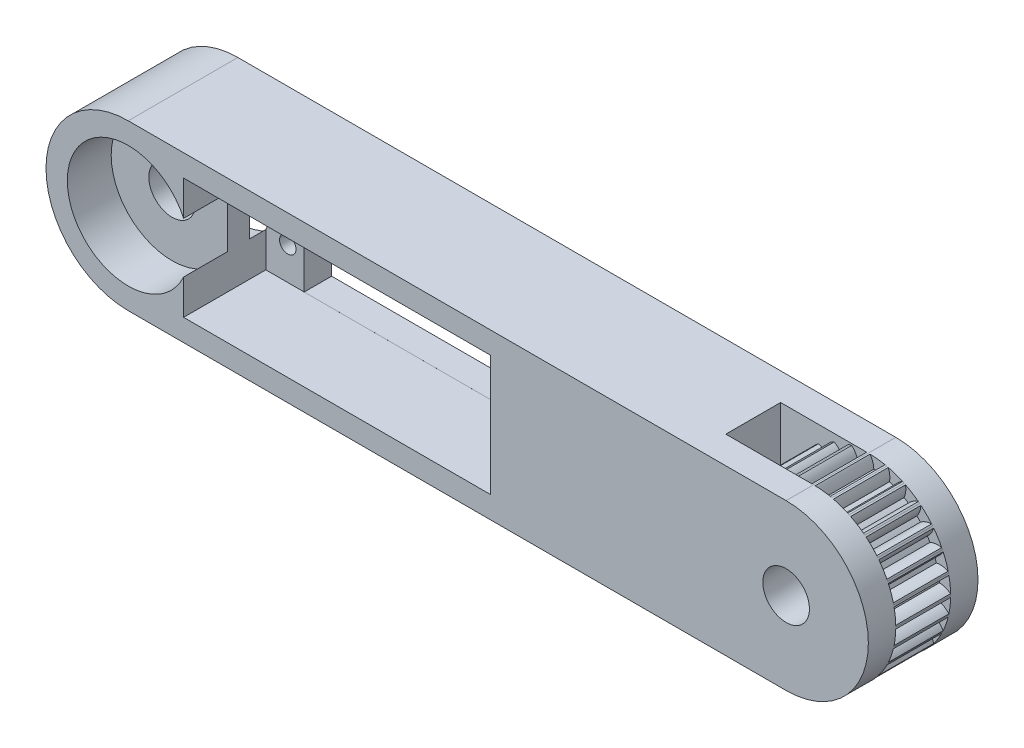
SolidWorks part; units mm, degrees
ref_plane "Front Plane" through (0, 0, 0) normal (0, 0, 1) x (1, 0, 0)
ref_plane "Top Plane" through (0, 0, 0) normal (0, 1, 0) x (1, 0, 0)
ref_plane "Right Plane" through (0, 0, 0) normal (1, 0, 0) x (0, 0, -1)
sketch "Sketch1" plane through (0, 0, 0) normal (0, 0, 1) x (1, 0, 0)
  line L0 (0, 0) -> (120, 0) construction
  line L1 (0, 15) -> (120, 15)
  line L2 (0, -15) -> (120, -15)
  circle A0 centre (0, 0) radius 15
  circle A1 centre (120, 0) radius 15
  dimension "D1" = 30
  dimension "D2" = 120
extrude "Boss-Extrude1" add sketch "Sketch1" along normal mid plane 20 contours A0 | A0 L0 A1 L1 | L0 A0 L2 A1 | A1 region at (60, 7.777, 0) region at (10.3066, -10.3066, 0) region at (60, -7.777, 0) region at (109.6934, 10.3066, 0)
sketch "Sketch9" plane through (0, 0, 10) normal (0, 0, 1) x (1, 0, 0)
  line L0 (0, 0) -> (120, 0) construction
  line L1 (104, 21.8549) -> (104, -22.7594)
  line L2 (104, -22.7594) -> (146.071, -22.7594)
  line L3 (146.071, -22.7594) -> (146.071, 21.8549)
  line L4 (146.071, 21.8549) -> (104, 21.8549)
  dimension "D1" = 120
  dimension "D2" = 16
sketch "Sketch3" plane through (0, 0, 10) normal (0, 0, 1) x (1, 0, 0)
  line L0 (0, 0) -> (120, 0) construction
  line L1 (120, 0) -> (120, -10.6139) construction
  line L2 (120.3, 15) -> (119.7, 15)
  circle A4 centre (120, 0) radius 13
  circle A5 centre (120, 0) radius 4.25
  circle A6 centre (120, 0) radius 15 construction
  arc A7 (119.7, 15) -> (119, 12.9615) centre (122.738, 12.8174) ccw
  arc A8 (120.3, 15) -> (121, 12.9615) centre (117.262, 12.8174) cw
  point P12 (119.2, 14.0322)
  point P14 (120, 15)
  arc M6 (120, -15) -> (120, 15) centre (120, 0) ccw
  line M7 (120, 15) -> (0, 15)
  dimension "D2" = 26
  dimension "D3" = 8.5
  dimension "D5" = 0.8
  dimension "D7" = 30
  dimension "D1" = 120
  dimension "D4" = 1
  dimension "D6" = 0.6
extrude "Cut-Extrude5" cut sketch "Sketch3" against normal through all contours A5 region at (120, 0, 10)
sketch "Sketch4" plane through (0, 0, 10) normal (0, 0, 1) x (1, 0, 0)
  line L0 (0, 0) -> (120, 0) construction
  line L2 (59.1, -11) -> (17.1, -11)
  line L3 (59.1, -11) -> (59.1, 11)
  line L4 (59.1, 11) -> (17.1, 11)
  line L5 (17.1, -11) -> (17.1, 11)
  line L6 (59.1, -11) -> (17.1, 11) construction
  line L7 (59.1, 11) -> (17.1, -11) construction
  circle A0 centre (0, 0) radius 4.25
  circle A1 centre (0, 0) radius 11.11
  point P4 (38.1, 0)
  dimension "D3" = 8.5
  dimension "D4" = 22.22
  dimension "D1" = 22
  dimension "D2" = 42
  dimension "D5" = 17.1
extrude "Cut-Extrude8" cut sketch "Sketch4" against normal through all contours A0 | L3 L2 L5 L4
sketch "Sketch5" plane through (0, 0, -10) normal (0, 0, -1) x (-1, 0, 0)
  circle A0 centre (0, 0) radius 11.11
  dimension "D1" = 22.22
extrude "Cut-Extrude10" cut sketch "Sketch5" against normal blind 8
mirror "Mirror2" about plane through (0, 0, 0) normal (0, 0, 1) of "Cut-Extrude10"
sketch "Sketch7" plane through (0, 0, 10) normal (0, 0, 1) x (1, 0, 0)
  line L0 (38.1, 11) -> (38.1, -11) construction
  line L1 (59.1, 11) -> (17.1, 11) construction
  line L2 (59.1, -11) -> (17.1, -11) construction
  line L4 (66.1, -11.0014) -> (10.1, -11.0014)
  line L5 (66.1, -11.0014) -> (66.1, 11.0014)
  line L6 (66.1, 11.0014) -> (10.1, 11.0014)
  line L7 (10.1, -11.0014) -> (10.1, 11.0014)
  line L8 (66.1, -11.0014) -> (10.1, 11.0014) construction
  line L9 (66.1, 11.0014) -> (10.1, -11.0014) construction
  point P6 (38.1, 0)
  dimension "D1" = 56
extrude "Cut-Extrude12" cut sketch "Sketch7" against normal blind 15
sketch "Sketch8" plane through (0, 0, -5) normal (0, 0, 1) x (1, 0, 0)
  line L0 (38.1, 11.0014) -> (38.1, -11.0014) construction
  line L1 (66.1, 11.0014) -> (10.1, 11.0014) construction
  line L2 (10.1, -11.0014) -> (66.1, -11.0014) construction
  line L3 (14.1, 5) -> (14.1, -5) construction
  line L4 (62.1, 5) -> (62.1, -5) construction
  line L5 (38.1, 0) -> (25.4065, 0) construction
  line L6 (14.1, 0) -> (20.8073, 0) construction
  circle A0 centre (14.1, 5) radius 1.5
  circle A1 centre (14.1, -5) radius 1.5
  circle A2 centre (62.1, -5) radius 1.5
  circle A3 centre (62.1, 5) radius 1.5
  dimension "D1" = 3
  dimension "D2" = 10
  dimension "D3" = 48
extrude "Cut-Extrude13" cut sketch "Sketch8" against normal blind 14 contours A0 | A1 | A2 | A3 region at (14.1, 5, -5) region at (14.1, -5, -5) region at (62.1, -5, -5)
sketch "Sketch13" plane through (0, 0, 0) normal (0, 0, 1) x (1, 0, 0)
  line L0 (120, 15) -> (104, 15)
  line L3 (104, 15) -> (104, -15)
  line L5 (104, -15) -> (120, -15)
  arc A0 (120, -15) -> (120, 15) centre (120, 0) ccw
  dimension "D1" = 16
extrude "Cut-Extrude17" cut sketch "Sketch13" against normal mid plane 10
extrude "Boss-Extrude2" add sketch "Sketch3<6>" against normal blind 10 from offset 5 contours A4 A5 region at (129.2696, 8.582, 10) offset against normal yes
sketch "Sketch3<6>" plane through (0, 0, 10) normal (0, 0, 1) x (1, 0, 0) same geometry as "Sketch3"
extrude "Boss-Extrude3" add sketch "Sketch3<7>" against normal blind 10 from offset 5 contours A8 A7 A4 M6 M7 region at (120, 13.842, 10) offset against normal yes
sketch "Sketch3<7>" plane through (0, 0, 10) normal (0, 0, 1) x (1, 0, 0) same geometry as "Sketch3"
pattern_circular "CirPattern1" count 28 over 360 of "Boss-Extrude3"
sketch "Sketch10" plane through (0, 0, -10) normal (0, 0, -1) x (-1, 0, 0)
  circle A0 centre (-120, 0) radius 9.5
  dimension "D1" = 19
extrude "Cut-Extrude15" cut sketch "Sketch10" against normal blind 5
sketch "Sketch11" plane through (0, 0, -10) normal (0, 0, -1) x (-1, 0, 0)
  circle A0 centre (-62.1, 5) radius 3.5
  circle A1 centre (-62.1, -5) radius 3.5
  circle A2 centre (-14.1, 5) radius 3.5
  circle A3 centre (-14.1, -5) radius 3.5
  dimension "D1" = 7
extrude "Cut-Extrude16" cut sketch "Sketch11" against normal blind 2
